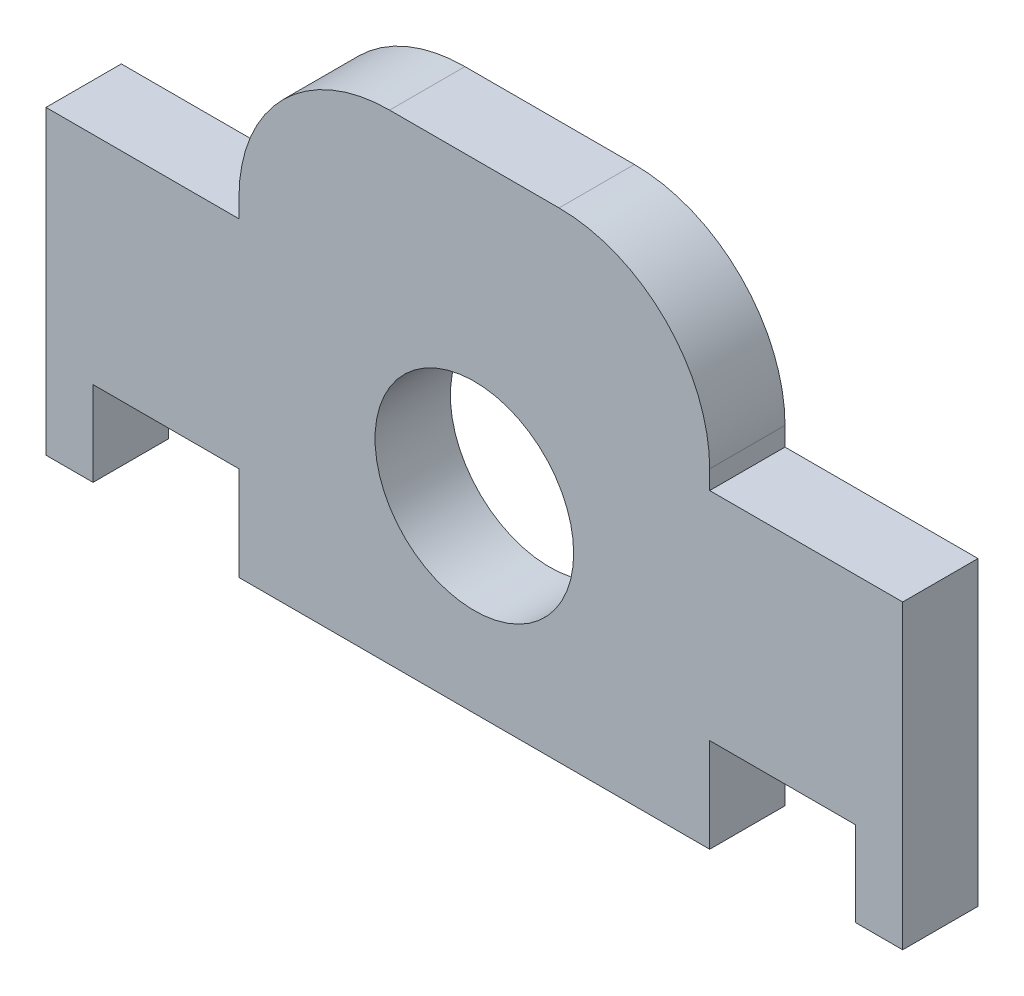
SolidWorks part; units mm, degrees
ref_plane "Front Plane" through (0, 0, 0) normal (0, 0, 1) x (1, 0, 0)
ref_plane "Top Plane" through (0, 0, 0) normal (0, 1, 0) x (1, 0, 0)
ref_plane "Right Plane" through (0, 0, 0) normal (1, 0, 0) x (0, 0, -1)
sketch "Sketch2" plane through (0, 0, 0) normal (0, 0, 1) x (1, 0, 0)
  line L0 (1.0743, 13.7948) -> (1.0743, -6.6552) construction
  line L1 (-33.9257, 13.7948) -> (36.0743, 13.7948)
  line L2 (-33.9257, 13.7948) -> (-33.9257, -37.2052)
  line L3 (-33.9257, -37.2052) -> (36.0743, -37.2052)
  line L4 (36.0743, 13.7948) -> (36.0743, -37.2052)
  line L5 (1.0743, -27.7552) -> (1.0743, -37.2052)
  line L6 (1.0743, -27.7552) -> (1.0743, -37.2052) construction
  circle A0 centre (1.0743, -17.2052) radius 10.55
  dimension "D4" = 21.1
  dimension "D1" = 70
  dimension "D2" = 51
  dimension "D3" = 20
extrude "Boss-Extrude1" add sketch "Sketch2" along normal blind 8 contours A0 L3 L4 L1 L2 region at (1.0743, 12.9287, 0)
sketch "Sketch3" plane through (0, 0, 8) normal (0, 0, 1) x (1, 0, 0)
  line L12 (26.0743, -37.2052) -> (36.0743, -37.2052)
  line L13 (-33.9257, -37.2052) -> (-23.9257, -37.2052)
  line L14 (-33.9257, -37.2052) -> (-33.9257, -27.2052)
  line L15 (-33.9257, -27.2052) -> (-23.9257, -27.2052)
  line L16 (-23.9257, -37.2052) -> (-23.9257, -27.2052)
  line L17 (26.0743, -37.2052) -> (26.0743, -27.2052)
  line L18 (26.0743, -27.2052) -> (36.0743, -27.2052)
  line L19 (36.0743, -37.2052) -> (36.0743, -27.2052)
  line L20 (-33.9257, 13.7948) -> (-23.9257, 13.7948)
  line L21 (-33.9257, 13.7948) -> (-33.9257, -4.2052)
  line L22 (-33.9257, -4.2052) -> (-23.9257, -4.2052)
  line L23 (-23.9257, -2.2052) -> (-23.9257, -4.2052)
  line L24 (36.0743, 13.7948) -> (26.0743, 13.7948)
  line L25 (36.0743, 13.7948) -> (36.0743, -4.2052)
  line L26 (36.0743, -4.2052) -> (26.0743, -4.2052)
  line L27 (26.0743, -2.2052) -> (26.0743, -4.2052)
  line L28 (-7.9257, 13.7948) -> (10.0743, 13.7948)
  arc A6 (-7.9257, 13.7948) -> (-23.9257, -2.2052) centre (-7.9257, -2.2052) ccw
  arc A7 (10.0743, 13.7948) -> (26.0743, -2.2052) centre (10.0743, -2.2052) cw
  line M5 (-33.9257, 13.7948) -> (-33.9257, -37.2052)
  line M7 (36.0743, -37.2052) -> (36.0743, 13.7948)
  line M8 (36.0743, 13.7948) -> (-33.9257, 13.7948)
  dimension "D5" = 10
  dimension "D6" = 16
  dimension "D11" = 16
  dimension "D2" = 10
  dimension "D3" = 18
  dimension "D4" = 18
  dimension "D7" = 10
  dimension "D8" = 10
  dimension "D9" = 10
  dimension "D10" = 10
extrude "Cut-Extrude1" cut sketch "Sketch3" against normal through all contours M8 M5 | M7 M8 | L14 L13 L16 L15 | L12 L19 L18 L17 region at (-26.9208, 6.0637, 8) region at (29.0694, 6.0637, 8)
sketch "Sketch5" plane through (0, -4.2052, 0) normal (0, 1, 0) x (1, 0, 0)
  line L1 (-33.9257, 0) -> (-39.4257, 0)
  line L2 (-33.9257, 0) -> (-33.9257, -8)
  line L3 (-33.9257, -8) -> (-39.4257, -8)
  line L4 (-39.4257, 0) -> (-39.4257, -8)
  line L6 (-39.4257, 0) -> (-44.4257, 0)
  line L7 (-39.4257, 0) -> (-39.4257, -8)
  line L8 (-39.4257, -8) -> (-44.4257, -8)
  line L9 (-44.4257, 0) -> (-44.4257, -8)
  line L10 (36.0743, 0) -> (41.5743, 0)
  line L11 (36.0743, 0) -> (36.0743, -8)
  line L12 (36.0743, -8) -> (41.5743, -8)
  line L13 (41.5743, 0) -> (41.5743, -8)
  line L14 (41.5743, -8) -> (46.5743, -8)
  line L15 (41.5743, -8) -> (41.5743, 0)
  line L16 (41.5743, 0) -> (46.5743, 0)
  line L17 (46.5743, -8) -> (46.5743, 0)
  line M10 (-33.9257, 0) -> (-33.9257, -8)
  dimension "D1" = 8
  dimension "D2" = 5.5
  dimension "D3" = 8
  dimension "D4" = 5
  dimension "D5" = 8
  dimension "D6" = 5.5
  dimension "D7" = 5
extrude "Boss-Extrude2" add sketch "Sketch5" against normal blind 23 contours L1 L4 L3 M10 region at (-36.6757, -4.2052, 4)
extrude "Boss-Extrude3" add sketch "Sketch5<3>" against normal blind 32 contours L6 L9 L8 L4 region at (-41.9257, -4.2052, 4)
sketch "Sketch5<3>" plane through (0, -4.2052, 0) normal (0, 1, 0) x (1, 0, 0) same geometry as "Sketch5"
extrude "Boss-Extrude4" add sketch "Sketch5<5>" against normal blind 32 separate body contours L14 L17 L16 L13 region at (44.0743, -4.2052, 4)
sketch "Sketch5<5>" plane through (0, -4.2052, 0) normal (0, 1, 0) x (1, 0, 0) same geometry as "Sketch5"
extrude "Boss-Extrude5" add sketch "Sketch5<6>" against normal blind 23 contours L13 L10 L11 L12 region at (38.8243, -4.2052, 4)
sketch "Sketch5<6>" plane through (0, -4.2052, 0) normal (0, 1, 0) x (1, 0, 0) same geometry as "Sketch5"
